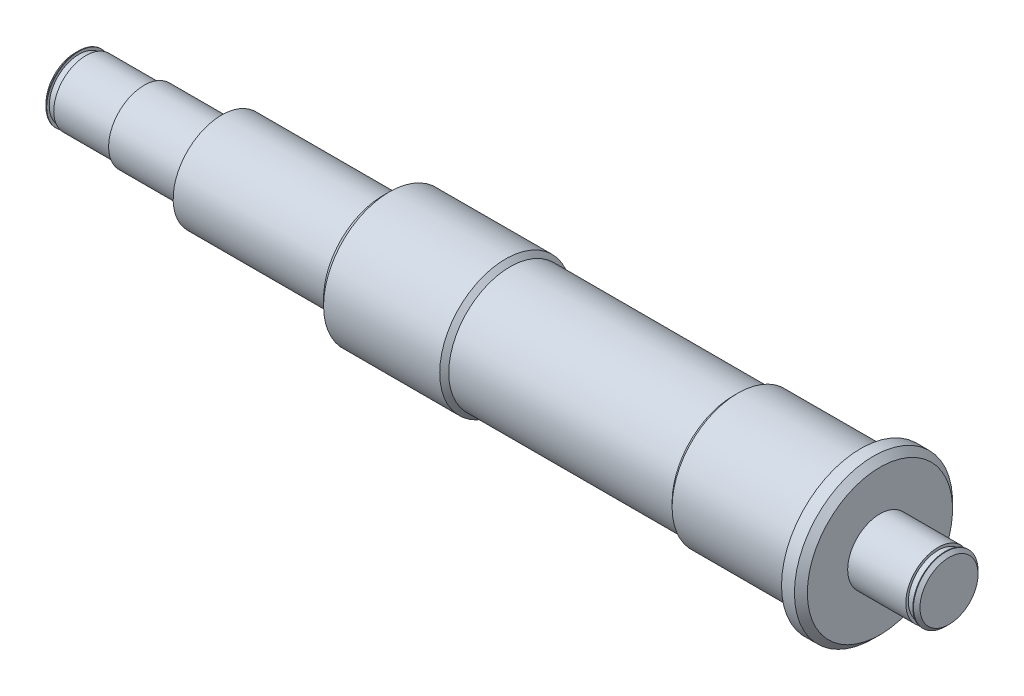
SolidWorks part; units mm, degrees
ref_plane "Płaszczyzna przednia" through (0, 0, 0) normal (0, 0, 1) x (1, 0, 0)
ref_plane "Płaszczyzna górna" through (0, 0, 0) normal (0, 1, 0) x (1, 0, 0)
ref_plane "Płaszczyzna prawa" through (0, 0, 0) normal (1, 0, 0) x (0, 0, -1)
sketch "Szkic1" plane through (0, 0, 0) normal (0, 0, 1) x (1, 0, 0)
  line L0 (0, 0) -> (0, 5)
  line L7 (47.7, 10.2) -> (67.7, 10.2)
  line L8 (67.7, 10.2) -> (67.7, 9.5)
  line L9 (67.7, 9.5) -> (101.7, 9.5)
  line L10 (101.7, 9.5) -> (101.7, 10.2)
  line L11 (101.7, 10.2) -> (121.7, 10.2)
  line L12 (121.7, 10.2) -> (121.7, 12.25)
  line L13 (121.7, 12.25) -> (124.7, 12.25)
  line L14 (124.7, 12.25) -> (124.7, 5)
  line L15 (124.7, 5) -> (133.7, 5)
  line L16 (135.4, 5) -> (135.4, 0)
  line L23 (135.4, 0) -> (0, 0)
  line L24 (-10.6747, 0) -> (-4.106, 0) construction
  line L25 (0, 5) -> (0.6, 5)
  line L26 (0.6, 5) -> (0.6, 4.6)
  line L27 (0.6, 4.6) -> (1.7, 4.6)
  line L28 (1.7, 4.6) -> (1.7, 5)
  line L29 (1.7, 5) -> (10.7, 5)
  line L30 (47.7, 7.5) -> (47.7, 10.2)
  line L33 (133.7, 5) -> (133.7, 4.6)
  line L34 (133.7, 4.6) -> (134.8, 4.6)
  line L35 (134.8, 4.6) -> (134.8, 5)
  line L36 (134.8, 5) -> (135.4, 5)
  line L37 (10.7, 5) -> (10.7, 5.5)
  line L38 (22.7, 7.5) -> (47.7, 7.5)
  line L39 (22.7, 7.5) -> (22.7, 5.5)
  line L40 (22.7, 5.5) -> (10.7, 5.5)
  point P23 (22.7, 6.5)
  dimension "D1" = 10
  dimension "D2" = 20.4
  dimension "D3" = 9
  dimension "D4" = 9
  dimension "D5" = 10
  dimension "D6" = 9.2
  dimension "D7" = 0.6
  dimension "D8" = 1.1
  dimension "D9" = 20
  dimension "D10" = 74
  dimension "D11" = 20
  dimension "D12" = 19
  dimension "D13" = 24.5
  dimension "D14" = 3
  dimension "D15" = 1.1
  dimension "D16" = 0.6
  dimension "D17" = 9.2
  dimension "D18" = 15
  dimension "D19" = 37
  dimension "D20" = 11
  dimension "D21" = 25
revolve "Obrót1" add sketch "Szkic1" angle 360 about L24
cosmetic thread "Oznaczenie gwintu1" parameters "D2"=11
chamfer "Sfazowanie1" distance 1 angle 45 4 edges at (101.7, 0, 10.2) (67.7, 0, 10.2) (124.7, 0, 12.25) (47.7, 0, 10.2)
chamfer "Sfazowanie2" distance 0.5 angle 45 2 edges at (135.4, 0, 5) (0, 0, 5)
sketch "Szkic2" plane through (22.7, 0, 0) normal (-1, 0, 0) x (0, 0, 1)
  line L0 (4.5, -6) -> (-4.5, -6)
  circle A0 centre (0, 0) radius 7.5 construction
  arc A1 (-4.5, -6) -> (4.5, -6) centre (0, 0) ccw
  point P4 (0, -6)
  point P5 (0, -7.5)
  dimension "D1" = 1.5
extrude "Wytnij-wyciągnięcie1" cut sketch "Szkic2" against normal up to surface (25 mm away) up to face at (47.7, 0, -9.2)
